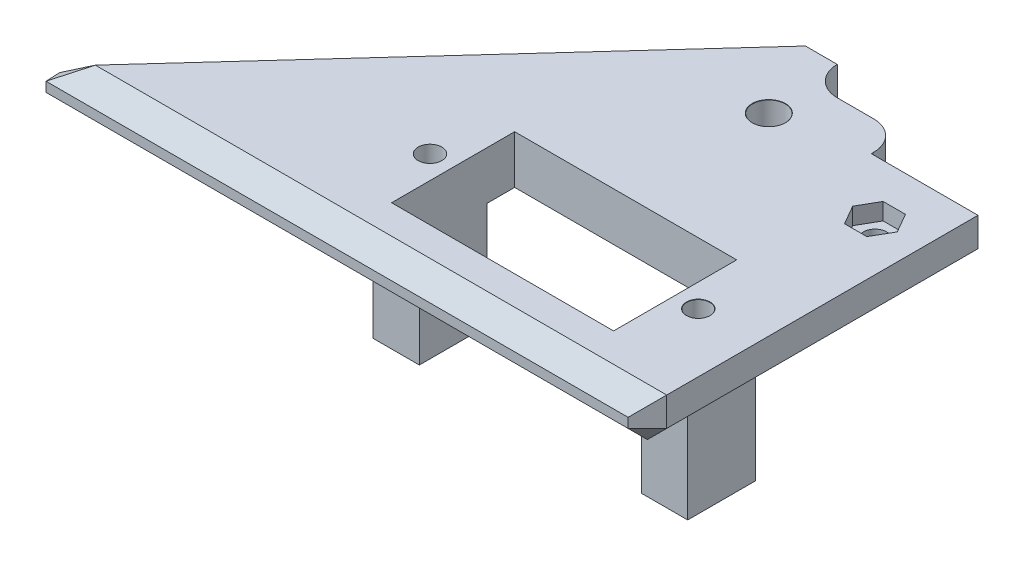
SolidWorks part; units mm, degrees
ref_plane "Front Plane" through (0, 0, 0) normal (0, 0, 1) x (1, 0, 0)
ref_plane "Top Plane" through (0, 0, 0) normal (0, 1, 0) x (1, 0, 0)
ref_plane "Right Plane" through (0, 0, 0) normal (1, 0, 0) x (0, 0, -1)
sketch "Sketch1" plane through (0, 0, 0) normal (0, 1, 0) x (1, 0, 0)
  line L0 (-3, 0) -> (-9, 0)
  line L5 (0, -3) -> (3.77, -3)
  line L6 (6.77, -6) -> (6.77, -6.5)
  line L7 (9.77, -6.5) -> (6.77, -6.5) construction
  line L8 (9.77, -9.5) -> (9.77, -15.5)
  line L9 (-9, 0) -> (-9, -15.5)
  line L10 (-9, -15.5) -> (9.77, -15.5)
  arc A0 (-3, 0) -> (0, -3) centre (0, 0) ccw
  arc A1 (6.77, -6) -> (3.77, -3) centre (3.77, -6) ccw
  arc A2 (6.77, -6.5) -> (9.77, -9.5) centre (9.77, -6.5) ccw
  dimension "D1" = 6
  dimension "D2" = 6
  dimension "D3" = 0.5
  dimension "D4" = 3.77
extrude "Boss-Extrude1" add sketch "Sketch1" along normal blind 5 contours L9 L10 L8 A2 L6 A1 L5 A0 L0
hole_wizard "M3 Clearance Hole1" positions "Sketch2" profile "Sketch3" hole size "M3" standard "ANSI Metric" end condition through all
sketch "Sketch2" plane through (0, 5, 0) normal (0, 1, 0) x (1, 0, 0)
  line L1 (-2.1713, -7.9213) -> (-2.1213, -7.9213) construction
  line L2 (-2.1213, -7.9213) -> (-2.1213, -2.1213) construction
  arc A1 (-3, 0) -> (0, -3) centre (0, 0) ccw construction
  point P0 (-2.1713, -7.9213)
  dimension "D1" = 5.8
  dimension "D2" = 0.05
sketch "Sketch3" plane through (-2.1713, 5, 7.9213) normal (1, 0, 0) x (0, 0, 1)
  line L0 (0, 0) -> (0, 5)
  line L1 (0, 5) -> (1.7, 5)
  line L2 (1.7, 5) -> (1.7, 0.025)
  line L3 (1.7, 0.025) -> (1.725, 0)
  line L5 (1.725, 0) -> (0, 0)
  line L6 (-1.7, 0.025) -> (-1.725, 0) construction
  line L11 (0, -6.35) -> (0, 107.95) construction
  dimension "Thru Hole Dia." = 3.4
  dimension "Thru Hole Depth" = 5
  dimension "Near C'Sink Dia." = 3.45
  dimension "Near C'Sink Angle" = 90
sketch "Sketch4" plane through (0, 5, 0) normal (0, 1, 0) x (1, 0, 0)
  line L0 (-9, -15.5) -> (9.77, -15.5) construction
  line L1 (-22.1713, -15.5) -> (17.8287, -15.5)
  line L2 (-22.1713, -15.5) -> (-22.1713, -40.5)
  line L3 (-22.1713, -40.5) -> (17.8287, -40.5)
  line L4 (17.8287, -40.5) -> (17.8287, -15.5)
  circle A0 centre (-2.1713, -7.9213) radius 1.725 construction
  circle A1 centre (-2.1713, -7.9213) radius 1.725 construction
  point P10 (-2.1713, -15.5)
  dimension "D1" = 40
  dimension "D2" = 25
extrude "Boss-Extrude2" add sketch "Sketch4" against normal up to surface (5 mm away) up to face at (-2.1713, 0, 9.6213)
sketch "Sketch5" plane through (0, 5, 0) normal (0, 1, 0) x (1, 0, 0)
  line L0 (17.8287, -15.5) -> (9.77, -15.5) construction
  line L1 (9.77, -9.5) -> (9.77, -15.5) construction
  line L2 (17.8287, -15.5) -> (9.77, -15.5)
  line L3 (9.77, -9.5) -> (9.77, -15.5)
  line L4 (9.77, -9.5) -> (17.8287, -9.5)
  line L5 (17.8287, -9.5) -> (17.8287, -15.5)
  line L13 (-9, 0) -> (-45.89, -40.5)
  line L14 (-45.89, -40.5) -> (-22.1713, -40.5)
  line L15 (-22.1713, -40.5) -> (-22.1713, -15.5)
  line L16 (-22.1713, -15.5) -> (-9, -15.5)
  line L17 (-9, -15.5) -> (-9, 0)
  dimension "D1" = 36.89
extrude "Boss-Extrude3" add sketch "Sketch5" against normal up to surface (5 mm away) up to face at (-2.1713, 0, 9.6213)
sketch "Sketch8" plane through (0, 5, 0) normal (0, 1, 0) x (1, 0, 0)
  line L0 (-23.1184, -15.5) -> (17.8287, -15.5) construction
  line L1 (17.8287, -40.5) -> (17.8287, -9.5) construction
  line L2 (-2.1713, -29.125) -> (-2.1713, -7.9213) construction
  line L3 (-13.6713, -22.75) -> (9.3287, -22.75)
  line L4 (-13.6713, -22.75) -> (-13.6713, -35.5)
  line L5 (-13.6713, -35.5) -> (9.3287, -35.5)
  line L6 (9.3287, -22.75) -> (9.3287, -35.5)
  line L7 (-13.6713, -22.75) -> (9.3287, -35.5) construction
  line L8 (-13.6713, -35.5) -> (9.3287, -22.75) construction
  line L9 (-45.89, -40.5) -> (17.8287, -40.5) construction
  line L10 (-9, 0) -> (-45.89, -40.5) construction
  line L11 (17.8287, -9.5) -> (9.77, -9.5) construction
  circle A1 centre (-2.1713, -7.9213) radius 1.725 construction
  circle A2 centre (-2.1713, -7.9213) radius 1.725 construction
  point P5 (-2.1713, -29.125)
  dimension "D1" = 23
  dimension "D2" = 12.75
  dimension "D3" = 5
  dimension "D4" = 6
extrude "Cut-Extrude1" cut sketch "Sketch8" against normal up to surface (5 mm away) contours L4 L5 L6 L3 up to face at (-2.1713, 0, 9.6213)
hole_wizard "M2 Clearance Hole1" positions "Sketch9" profile "Sketch10" hole size "M2" standard "ANSI Metric" end condition through all
sketch "Sketch9" plane through (0, 5, 0) normal (0, 1, 0) x (1, 0, 0)
  line L0 (-16.0713, -29.125) -> (11.7287, -29.125) construction
  line L1 (-2.1713, -29.125) -> (-2.1713, -22.75) construction
  line L2 (-13.6713, -22.75) -> (9.3287, -22.75) construction
  line L3 (-2.1713, -29.125) -> (-2.1713, -35.5) construction
  line L4 (-13.6713, -35.5) -> (9.3287, -35.5) construction
  point P0 (-16.0713, -29.125)
  point P2 (11.7287, -29.125)
  dimension "D1" = 27.8
sketch "Sketch10" plane through (-16.0713, 5, 29.125) normal (1, 0, 0) x (0, 0, 1)
  line L0 (0, 0) -> (0, 5)
  line L1 (0, 5) -> (1.2, 5)
  line L2 (1.2, 5) -> (1.2, 0.025)
  line L3 (1.2, 0.025) -> (1.225, 0)
  line L5 (1.225, 0) -> (0, 0)
  line L6 (-1.2, 0.025) -> (-1.225, 0) construction
  line L11 (0, -6.35) -> (0, 107.95) construction
  dimension "Thru Hole Dia." = 2.4
  dimension "Thru Hole Depth" = 5
  dimension "Near C'Sink Dia." = 2.45
  dimension "Near C'Sink Angle" = 90
sketch "Sketch11" plane through (0, 0, 0) normal (0, -1, 0) x (1, 0, 0)
  line L0 (-13.6713, 35.5) -> (-13.6713, 22.75) construction
  line L1 (-13.6713, 32.625) -> (-18.4713, 32.625)
  line L2 (-13.6713, 32.625) -> (-13.6713, 25.625)
  line L3 (-13.6713, 25.625) -> (-18.4713, 25.625)
  line L4 (-18.4713, 32.625) -> (-18.4713, 25.625)
  line L5 (-13.6713, 32.625) -> (-18.4713, 25.625) construction
  line L6 (-13.6713, 25.625) -> (-18.4713, 32.625) construction
  line L7 (14.1287, 32.625) -> (9.3287, 32.625)
  line L8 (14.1287, 32.625) -> (14.1287, 25.625)
  line L9 (14.1287, 25.625) -> (9.3287, 25.625)
  line L10 (9.3287, 32.625) -> (9.3287, 25.625)
  line L11 (14.1287, 32.625) -> (9.3287, 25.625) construction
  line L12 (14.1287, 25.625) -> (9.3287, 32.625) construction
  point P0 (-16.0713, 29.125)
  point P6 (11.7287, 29.125)
  dimension "D1" = 7
extrude "Boss-Extrude4" add sketch "Sketch11" along normal blind 11
sketch "Sketch12" plane through (0, -11, 0) normal (0, -1, 0) x (1, 0, 0)
  line L1 (-16.0713, 26.8156) -> (-14.0713, 27.9703)
  line L2 (-14.0713, 27.9703) -> (-14.0713, 30.2797)
  line L3 (-14.0713, 30.2797) -> (-16.0713, 31.4344)
  line L4 (-16.0713, 31.4344) -> (-18.0713, 30.2797)
  line L5 (-18.0713, 30.2797) -> (-18.0713, 27.9703)
  line L6 (-18.0713, 27.9703) -> (-16.0713, 26.8156)
  line L7 (11.7287, 26.8156) -> (13.7287, 27.9703)
  line L8 (13.7287, 27.9703) -> (13.7287, 30.2797)
  line L9 (13.7287, 30.2797) -> (11.7287, 31.4344)
  line L10 (11.7287, 31.4344) -> (9.7287, 30.2797)
  line L11 (9.7287, 30.2797) -> (9.7287, 27.9703)
  line L12 (9.7287, 27.9703) -> (11.7287, 26.8156)
  circle A0 centre (11.7287, 29.125) radius 1.2 construction
  circle A1 centre (-16.0713, 29.125) radius 1.2 construction
  circle A2 centre (11.7287, 29.125) radius 1.2 construction
  circle A3 centre (-16.0713, 29.125) radius 1.2 construction
  circle A4 centre (-16.0713, 29.125) radius 2 construction
  circle A5 centre (11.7287, 29.125) radius 2 construction
  dimension "D1" = 4
extrude "Cut-Extrude2" cut sketch "Sketch12" against normal blind 1.75
sketch "Sketch13" plane through (0, -9.25, 0) normal (0, -1, 0) x (1, 0, 0)
  circle A0 centre (-16.0713, 29.125) radius 1.225 construction
  circle A1 centre (11.7287, 29.125) radius 1.2 construction
  circle A2 centre (-16.0713, 29.125) radius 1.225
  circle A3 centre (11.7287, 29.125) radius 1.2
extrude "Cut-Extrude3" cut sketch "Sketch13" against normal up to surface (14.25 mm away) up to face at (-16.0713, 5, 30.35)
chamfer "Chamfer1" distance 2 angle 45 8 edges at (-14.0307, 5, 40.5) (17.8287, 2.5, 9.5) (17.8287, 2.5, 40.5) (17.8287, 0, 25) (-14.0307, 0, 40.5) (-27.445, 5, 20.25) (-45.89, 2.5, 40.5) (-27.445, 0, 20.25) first distance on face at (-16.0713, 5, 30.35) first distance on face at (17.8287, 2.5, 25) first distance on face at (0.4226, 0, 11.9121) first distance on face at (-27.445, 2.5, 20.25)
hole_wizard "M2 Clearance Hole2" positions "Sketch16" profile "Sketch17" hole size "M2" standard "ANSI Metric"
sketch "Sketch16" plane through (0, 5, 0) normal (0, 1, 0) x (1, 0, 0)
  line L0 (-2.1713, -7.9213) -> (-2.1713, -11.9213) construction
  line L1 (-2.1713, -11.9213) -> (12.8287, -11.9213) construction
  point P0 (12.8287, -11.9213)
  dimension "D1" = 4
  dimension "D2" = 15
sketch "Sketch17" plane through (12.8287, 5, 11.9213) normal (1, 0, 0) x (0, 0, 1)
  line L0 (0, 0) -> (0, 5.721)
  line L1 (0, 5.721) -> (1.2, 5)
  line L2 (1.2, 5) -> (1.2, 0.025)
  line L3 (1.2, 0.025) -> (1.225, 0)
  line L5 (1.225, 0) -> (0, 0)
  line L6 (-1.2, 0.025) -> (-1.225, 0) construction
  line L10 (0, 5.721) -> (-1.2, 5) construction
  line L11 (0, -6.35) -> (0, 107.95) construction
  dimension "Hole Dia." = 2.4
  dimension "Hole Depth" = 5
  dimension "Near C'Sink Dia." = 2.45
  dimension "Near C'Sink Angle" = 90
  dimension "Drill Angle" = 118
sketch "Sketch18" plane through (0, 5, 0) normal (0, 1, 0) x (1, 0, 0)
  line L1 (11.674, -13.9213) -> (13.9834, -13.9213)
  line L2 (13.9834, -13.9213) -> (15.1381, -11.9213)
  line L3 (15.1381, -11.9213) -> (13.9834, -9.9213)
  line L4 (13.9834, -9.9213) -> (11.674, -9.9213)
  line L5 (11.674, -9.9213) -> (10.5193, -11.9213)
  line L6 (10.5193, -11.9213) -> (11.674, -13.9213)
  circle A0 centre (12.8287, -11.9213) radius 2 construction
  dimension "D1" = 4
extrude "Cut-Extrude4" cut sketch "Sketch18" against normal blind 1.75
sketch "Sketch19" plane through (0, 5, 0) normal (0, 1, 0) x (1, 0, 0)
  line L2 (17.8287, -6.25) -> (17.8287, -11.5)
  line L3 (15.8287, -9.5) -> (9.77, -9.5) construction
  line L4 (17.8287, -11.5) -> (15.8287, -9.5) construction
  line L5 (15.8287, -9.5) -> (9.77, -9.5)
  line L6 (17.8287, -11.5) -> (15.8287, -9.5)
  line L7 (6.77, -6.25) -> (17.8287, -6.25)
  line L8 (6.77, -6) -> (6.77, -6.5) construction
  line L9 (6.77, -6.25) -> (6.77, -6.5)
  arc A0 (6.77, -6.5) -> (9.77, -9.5) centre (9.77, -6.5) ccw construction
  arc A3 (6.77, -6.5) -> (9.77, -9.5) centre (9.77, -6.5) ccw
extrude "Boss-Extrude5" add sketch "Sketch19" against normal up to surface (5 mm away) up to face at (12.8287, 0, 13.1213)
chamfer "Chamfer2" distance 2 angle 45 1 edges at (17.8287, 0, 8.875)
